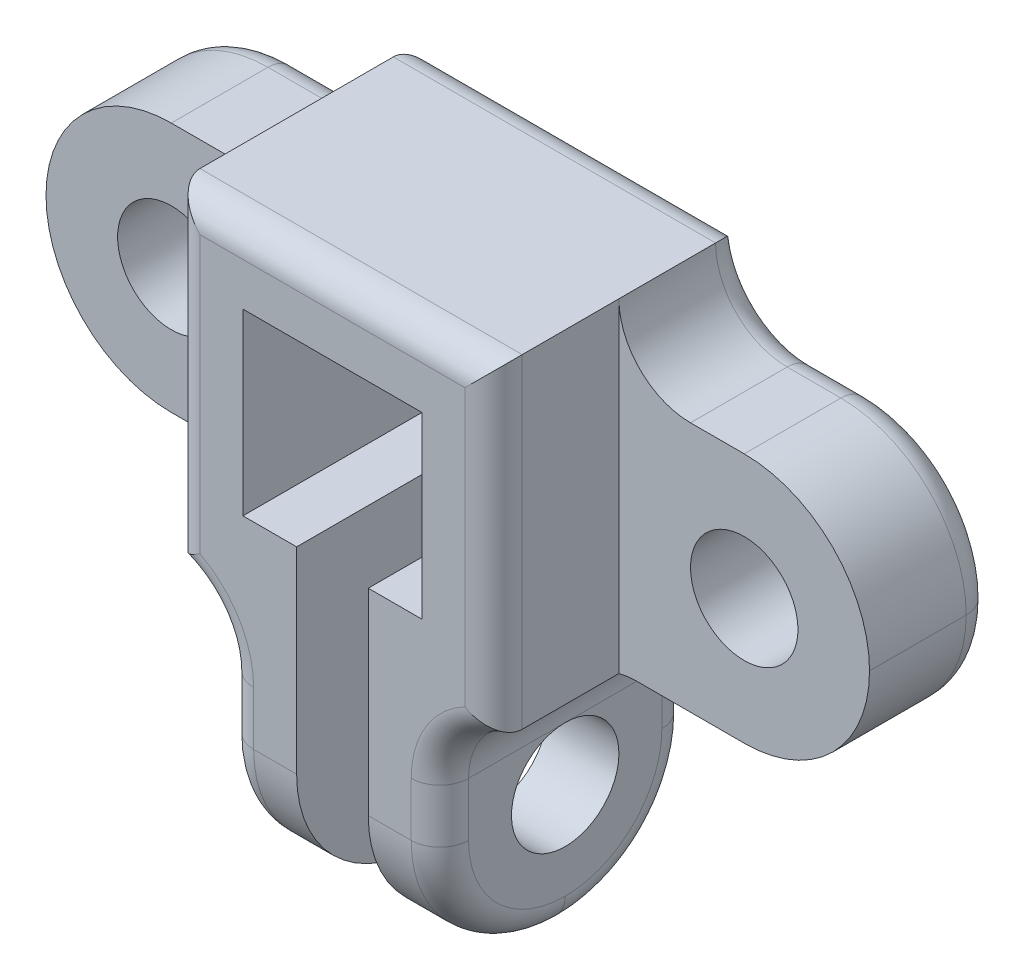
SolidWorks part; units mm, degrees
ref_plane "前视基准面" through (0, 0, 0) normal (0, 0, 1) x (1, 0, 0)
ref_plane "上视基准面" through (0, 0, 0) normal (0, 1, 0) x (1, 0, 0)
ref_plane "右视基准面" through (0, 0, 0) normal (1, 0, 0) x (0, 0, -1)
sketch "草图1" plane through (0, 0, 0) normal (0, 0, 1) x (1, 0, 0)
  line L0 (-2.5, 2.5) -> (-11.5, 2.5)
  line L1 (-2.5, 2.5) -> (2.5, 2.5)
  line L2 (-2.5, 2.5) -> (-2.5, -2.5)
  line L3 (-2.5, -2.5) -> (2.5, -2.5)
  line L4 (2.5, 2.5) -> (2.5, -2.5)
  line L5 (-2.5, 2.5) -> (2.5, -2.5) construction
  line L6 (-2.5, -2.5) -> (2.5, 2.5) construction
  line L7 (-4.5, 4.5) -> (4.5, 4.5)
  line L8 (-4.5, 4.5) -> (-4.5, -4.5)
  line L9 (-4.5, -4.5) -> (4.5, -4.5)
  line L10 (4.5, 4.5) -> (4.5, -4.5)
  line L11 (-4.5, 4.5) -> (4.5, -4.5) construction
  line L12 (-4.5, -4.5) -> (4.5, 4.5) construction
  line L13 (-11.5, 2.5) -> (-11.5, -4.5)
  line L14 (-11.5, -4.5) -> (-4.5, -4.5)
  line L15 (0, 9.7861) -> (0, -13.7093) construction
  line L16 (11.5, -4.5) -> (4.5, -4.5)
  line L17 (11.5, 2.5) -> (11.5, -4.5)
  line L18 (2.5, 2.5) -> (11.5, 2.5)
  line L19 (-1, -2.5) -> (-1, -11.5)
  line L20 (-1, -11.5) -> (-3, -11.5)
  line L21 (-3, -11.5) -> (-3, -4.5)
  line L22 (1, -11.5) -> (3, -11.5)
  line L23 (1, -2.5) -> (1, -11.5)
  line L24 (3, -11.5) -> (3, -4.5)
  point P0 (0, 0)
  point P5 (0, 0)
  dimension "D1" = 5
  dimension "D2" = 5
  dimension "D3" = 9
  dimension "D4" = 9
  dimension "D5" = 7
  dimension "D6" = 7
  dimension "D7" = 1
  dimension "D8" = 2
  dimension "D9" = 7
extrude "凸台-拉伸1" add sketch "草图1" along normal blind 7 contours L19 L3 L2 L0 L8 L9 | L1 L18 L10 L7 L8 L0 | L3 L23 L9 L10 L18 L4 | L21 L20 L19 L9 | L22 L24 L9 L23 | L13 L14 L8 L0 | L18 L10 L16 L17 region at (-3.1912, -1.4412, 0) region at (0, 3.5, 0) region at (-8, -1, 0) region at (3.1912, -1.4412, 0) region at (8, -1, 0) region at (-2, -8, 0) region at (2, -8, 0)
sketch "草图2" plane through (0, 0, 7) normal (0, 0, 1) x (1, 0, 0)
  line L0 (-4.5, 2.5) -> (-4.5, -4.5)
  line L1 (-11.5, -4.5) -> (-3, -4.5) construction
  line L2 (-4.5, -4.5) -> (-11.5, -4.5)
  line L3 (-11.5, -4.5) -> (-11.5, 2.5)
  line L4 (-11.5, 2.5) -> (-4.5, 2.5)
  line L5 (4.5, 2.5) -> (4.5, -4.5)
  line L6 (3, -4.5) -> (11.5, -4.5) construction
  line L7 (4.5, -4.5) -> (11.5, -4.5)
  line L8 (11.5, -4.5) -> (11.5, 2.5)
  line L9 (11.5, 2.5) -> (4.5, 2.5)
extrude "切除-拉伸1" cut sketch "草图2" against normal blind 3.5
fillet "圆角1" radius 3.5 8 edges at (2, -11.5, 0) (2, -11.5, 7) (-2, -11.5, 0) (-2, -11.5, 7) (11.5, -4.5, 1.75) (11.5, 2.5, 1.75) (-11.5, -4.5, 1.75) (-11.5, 2.5, 1.75)
sketch "草图3" plane through (0, 0, 3.5) normal (0, 0, 1) x (1, 0, 0)
  line L0 (0, 6.7575) -> (0, -12.0405) construction
  circle A0 centre (-8, -1) radius 1.5
  circle A1 centre (8, -1) radius 1.5
  dimension "D1" = 3
extrude "切除-拉伸2" cut sketch "草图3" against normal through all
sketch "草图4" plane through (-3, 0, 0) normal (-1, 0, 0) x (0, 0, 1)
  circle A0 centre (3.5, -8) radius 1.5
  dimension "D1" = 3
extrude "切除-拉伸3" cut sketch "草图4" against normal through all
fillet "圆角2" radius 2 2 edges at (4.5, 2.5, 1.75) (-4.5, 2.5, 1.75)
fillet "圆角3" radius 2 2 edges at (3, -4.5, 3.5) (-3, -4.5, 3.5)
fillet "圆角4" radius 0.8 26 edges at (5.0858, 3.0858, 0) (7.25, 2.5, 0) (10.4749, 1.4749, 0) (10.4749, -3.4749, 0) (6.5, -4.5, 0) (3, -7.25, 7) (3, -10.4749, 5.9749) (3, -10.4749, 1.0251) (3, -7.25, 0) (-5.0858, 3.0858, 0) (-7.25, 2.5, 0) (-10.4749, 1.4749, 0) (-10.4749, -3.4749, 0) (-6.5, -4.5, 0) (-3.5858, -5.0858, 0) (-3, -7.25, 0) (-3, -10.4749, 1.0251) (-3, -10.4749, 5.9749) (-3, -7.25, 7) (3.4189, -5.2753, 7) (3.5858, -5.0858, 0) (0, 4.5, 0) (0, 4.5, 7) (-3.4189, -5.2753, 7) (4.5, -0.0318, 7) (-4.5, -0.0318, 7)
